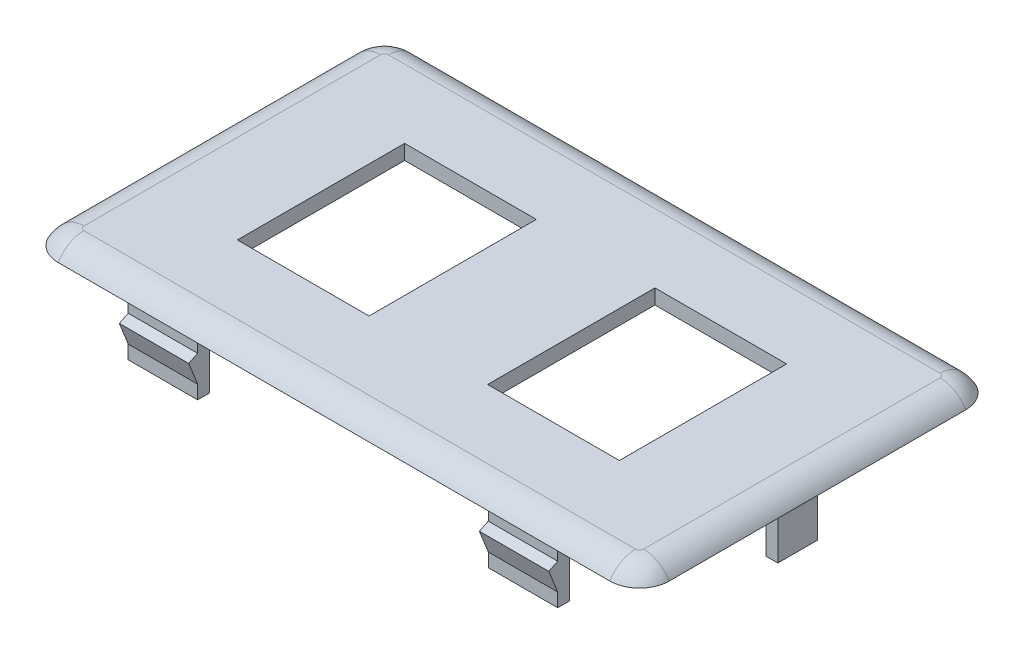
SolidWorks part; units mm, degrees
ref_plane "Front Plane" through (0, 0, 0) normal (0, 0, 1) x (1, 0, 0)
ref_plane "Top Plane" through (0, 0, 0) normal (0, 1, 0) x (1, 0, 0)
ref_plane "Right Plane" through (0, 0, 0) normal (1, 0, 0) x (0, 0, -1)
sketch "Sketch1" plane through (0, 0, 0) normal (0, 1, 0) x (1, 0, 0)
  line L1 (-46.5, 30) -> (46.5, 30)
  line L2 (-51.5, 25) -> (-51.5, -25)
  line L3 (-46.5, -30) -> (46.5, -30)
  line L4 (51.5, 25) -> (51.5, -25)
  line L5 (-51.5, 30) -> (51.5, -30) construction
  line L6 (-51.5, -30) -> (51.5, 30) construction
  arc A0 (46.5, -30) -> (51.5, -25) centre (46.5, -25) ccw
  arc A1 (51.5, 25) -> (46.5, 30) centre (46.5, 25) ccw
  arc A2 (-46.5, -30) -> (-51.5, -25) centre (-46.5, -25) cw
  arc A3 (-46.5, 30) -> (-51.5, 25) centre (-46.5, 25) ccw
  point P0 (0, 0)
  dimension "D3" = 5
  dimension "D1" = 103
  dimension "D2" = 60
extrude "Boss-Extrude1" add sketch "Sketch1" along normal blind 2.5
fillet "Fillet1" radius 5 8 edges at (-50.0355, 2.5, -28.5355) (0, 2.5, -30) (50.0355, 2.5, -28.5355) (51.5, 2.5, 0) (50.0355, 2.5, 28.5355) (0, 2.5, 30) (-50.0355, 2.5, 28.5355) (-51.5, 2.5, 0)
sketch "Sketch2" plane through (0, 0, 0) normal (0, -1, 0) x (1, 0, 0)
  line L0 (0, 30) -> (0, -30) construction
  line L1 (-36.2, 28.5) -> (-24.5, 28.5)
  line L2 (-36.2, 28.5) -> (-36.2, 26.5)
  line L3 (-36.2, 26.5) -> (-31.35, 26.5)
  line L4 (-24.5, 28.5) -> (-24.5, 26.5)
  line L5 (-46.5, 30) -> (46.5, 30) construction
  line L6 (46.5, -30) -> (-46.5, -30) construction
  line L7 (-51.5, 0) -> (51.5, 0) construction
  line L8 (-51.5, -25) -> (-51.5, 25) construction
  line L9 (51.5, 25) -> (51.5, -25) construction
  line L10 (48.225, -3.2828) -> (46.225, -3.2828)
  line L11 (24.5, 28.5) -> (36.2, 28.5)
  line L12 (24.5, 28.5) -> (24.5, 26.5)
  line L13 (24.5, 26.5) -> (29.35, 26.5)
  line L14 (36.2, 28.5) -> (36.2, 26.5)
  line L15 (24.5, -26.5) -> (29.35, -26.5)
  line L16 (24.5, -26.5) -> (24.5, -28.5)
  line L17 (24.5, -28.5) -> (36.2, -28.5)
  line L18 (36.2, -26.5) -> (36.2, -28.5)
  line L19 (-36.2, -28.5) -> (-24.5, -28.5)
  line L20 (-36.2, -28.5) -> (-36.2, -26.5)
  line L21 (-36.2, -26.5) -> (-31.35, -26.5)
  line L22 (-24.5, -28.5) -> (-24.5, -26.5)
  line L23 (-48.225, 3.4172) -> (-46.225, 3.4172)
  line L24 (-48.225, 3.4172) -> (-48.225, -3.2828)
  line L25 (-48.225, -3.2828) -> (-46.225, -3.2828)
  line L26 (-46.225, 3.4172) -> (-46.225, 1)
  line L27 (46.225, 3.4172) -> (46.225, 1)
  line L28 (48.225, 3.4172) -> (46.225, 3.4172)
  line L29 (48.225, 3.4172) -> (48.225, -3.2828)
  line L30 (-46.225, -0.9998) -> (-46.225, -3.2828)
  line L31 (-46.225, 1) -> (-40.225, 1)
  line L33 (-46.225, -0.9998) -> (-40.225, -0.9998)
  line L34 (-40.225, 1) -> (-40.225, -0.9998)
  line L35 (40.225, 1) -> (40.225, -0.9998)
  line L36 (46.225, 1) -> (40.225, 1)
  line L37 (46.225, -0.9998) -> (40.225, -0.9998)
  line L38 (46.225, -0.9998) -> (46.225, -3.2828)
  line L39 (-30.35, 28.5) -> (-30.35, -31.9661) construction
  line L40 (30.35, 28.5) -> (30.35, -35.5794) construction
  line L41 (-29.35, 26.5) -> (-24.5, 26.5)
  line L43 (-31.35, 26.5) -> (-31.35, 20.5)
  line L44 (-31.35, 20.5) -> (-29.35, 20.5)
  line L45 (-29.35, 26.5) -> (-29.35, 20.5)
  line L46 (-29.35, -26.5) -> (-24.5, -26.5)
  line L48 (-31.35, -26.5) -> (-31.35, -20.5)
  line L49 (-31.35, -20.5) -> (-29.35, -20.5)
  line L50 (-29.35, -26.5) -> (-29.35, -20.5)
  line L51 (31.35, -26.5) -> (36.2, -26.5)
  line L53 (29.35, 26.5) -> (29.35, 20.5)
  line L54 (29.35, 20.5) -> (31.35, 20.5)
  line L55 (31.35, 26.5) -> (31.35, 20.5)
  line L57 (29.35, -26.5) -> (29.35, -20.5)
  line L58 (29.35, -20.5) -> (31.35, -20.5)
  line L59 (31.35, -26.5) -> (31.35, -20.5)
  line L60 (31.35, 26.5) -> (36.2, 26.5)
  dimension "D1" = 2
  dimension "D2" = 11.7
  dimension "D3" = 2
  dimension "D4" = 11.7
  dimension "D5" = 49
  dimension "D6" = 24.5
  dimension "D7" = 24.5
  dimension "D8" = 15.3
  dimension "D9" = 2
  dimension "D11" = 26.5
  dimension "D12" = 2
  dimension "D13" = 11.7
  dimension "D14" = 49
  dimension "D15" = 24.5
  dimension "D16" = 2
  dimension "D17" = 6.7
  dimension "D18" = 46.225
  dimension "D19" = 6
  dimension "D20" = 1.9998
  dimension "D21" = 1
  dimension "D22" = 6
  dimension "D23" = 1
  dimension "D24" = 2
  dimension "D25" = 6
  dimension "D26" = 2
  dimension "D27" = 1
  dimension "D28" = 6
  dimension "D29" = 2
  dimension "D30" = 1
  dimension "D31" = 2
  dimension "D32" = 1
  dimension "D33" = 6
extrude "Boss-Extrude2" add sketch "Sketch2" along normal blind 9.8
sketch "Sketch4" plane through (0, 0, -0.9998) normal (0, 0, -1) x (-1, 0, 0)
  line L0 (40.225, 0) -> (46.225, -9.8)
  line L1 (46.225, -9.8) -> (40.225, -9.8)
  line L2 (40.225, -9.8) -> (40.225, 0)
extrude "Cut-Extrude1" cut sketch "Sketch4" against normal blind 9.8
mirror "Mirror1" about plane through (0, 0, 0) normal (1, 0, 0) of "Cut-Extrude1"
sketch "Sketch5" plane through (-31.35, 0, 0) normal (-1, 0, 0) x (0, 0, 1)
  line L0 (-26.5, -9.8) -> (-20.5, 0)
  line L1 (-20.5, 0) -> (-20.5, -9.8)
  line L2 (-20.5, -9.8) -> (-26.5, -9.8)
extrude "Cut-Extrude2" cut sketch "Sketch5" against normal through all
mirror "Mirror2" about plane through (0, 0, 0) normal (0, 0, 1) of "Cut-Extrude2"
sketch "Sketch6" plane through (36.2, 0, 0) normal (1, 0, 0) x (0, 0, -1)
  line L0 (-28.5, -3) -> (-28.5, -7.5)
  line L1 (-28.5, -9.8) -> (-28.5, 0) construction
  line L2 (-28.5, -3) -> (-30, -3.7261)
  line L3 (-30, -3.7261) -> (-28.5, -7.5)
  dimension "D1" = 4.5
  dimension "D2" = 1.5
  dimension "D3" = 3
extrude "Boss-Extrude3" add sketch "Sketch6" against normal blind 11.7
mirror "Mirror3" about plane through (0, 0, 0) normal (1, 0, 0) of "Boss-Extrude3"
mirror "Mirror4" about plane through (0, 0, 0) normal (0, 0, 1) of "Mirror3"
sketch "Sketch8" plane through (0, 0, 0) normal (0, -1, 0) x (1, 0, 0)
  line L0 (-51.5, 0) -> (51.5, 0) construction
  line L1 (-51.5, -25) -> (-51.5, 25) construction
  line L2 (51.5, 25) -> (51.5, -25) construction
  line L3 (0, 30) -> (0, -30) construction
  line L4 (-46.5, 30) -> (46.5, 30) construction
  line L5 (46.5, -30) -> (-46.5, -30) construction
  line L7 (-32.2, 14.1) -> (-10, 14.1)
  line L8 (-32.2, 14.1) -> (-32.2, -14.1)
  line L9 (-32.2, -14.1) -> (-10, -14.1)
  line L10 (-10, 14.1) -> (-10, -14.1)
  line L11 (10, 14.1) -> (32.2, 14.1)
  line L12 (10, 14.1) -> (10, -14.1)
  line L13 (10, -14.1) -> (32.2, -14.1)
  line L14 (32.2, 14.1) -> (32.2, -14.1)
  dimension "D1" = 28.2
  dimension "D2" = 22.2
  dimension "D3" = 28.2
  dimension "D4" = 22.2
  dimension "D5" = 14.1
  dimension "D6" = 14.1
  dimension "D7" = 10
  dimension "D8" = 10
extrude "Cut-Extrude3" cut sketch "Sketch8" against normal blind 10
